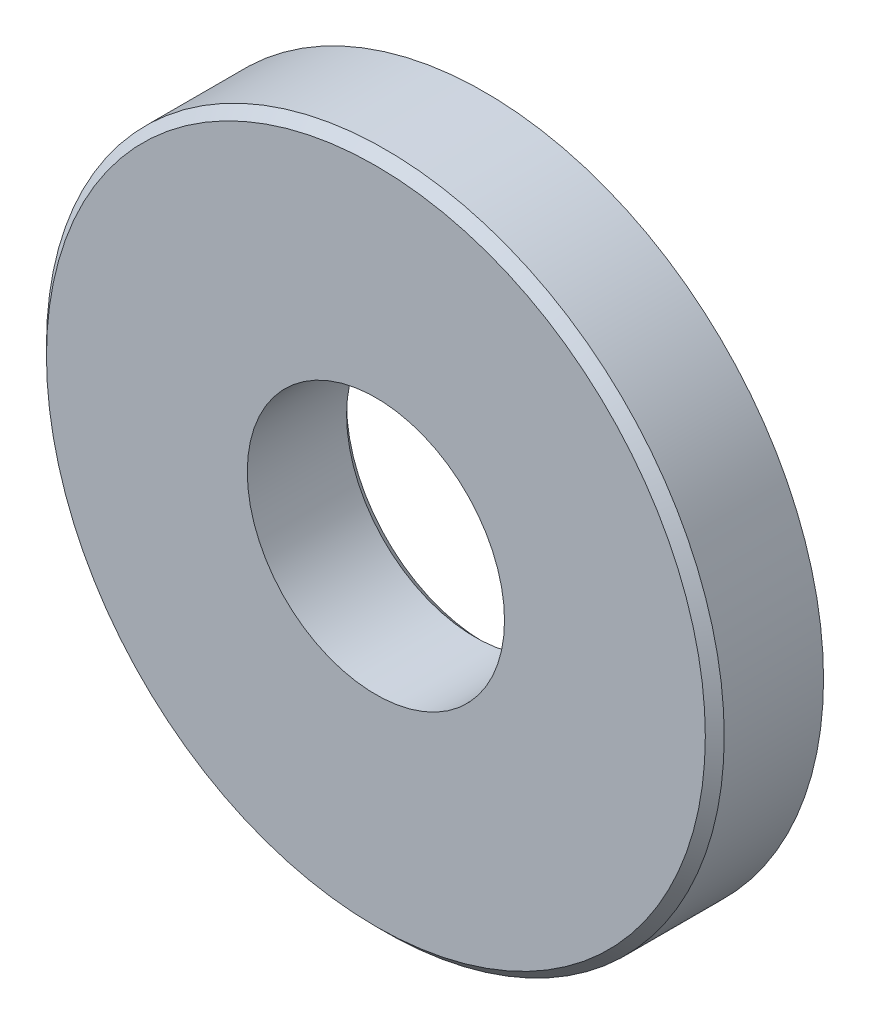
SolidWorks part; units mm, degrees
ref_plane "前视基准面" through (0, 0, 0) normal (0, 0, 1) x (1, 0, 0)
ref_plane "上视基准面" through (0, 0, 0) normal (0, 1, 0) x (1, 0, 0)
ref_plane "右视基准面" through (0, 0, 0) normal (1, 0, 0) x (0, 0, -1)
sketch "草图1" plane through (0, 0, 0) normal (0, 0, 1) x (1, 0, 0)
  circle A0 centre (0, 0) radius 4.08
  circle A1 centre (0, 0) radius 10.75
extrude "凸台-拉伸1" add sketch "草图1" along normal blind 3.45
chamfer "倒角1" distance 0.3 angle 45 1 edges at (10.75, 0, 3.45)
chamfer "倒角2" distance 0.3 angle 45 1 edges at (4.08, 0, 0)
